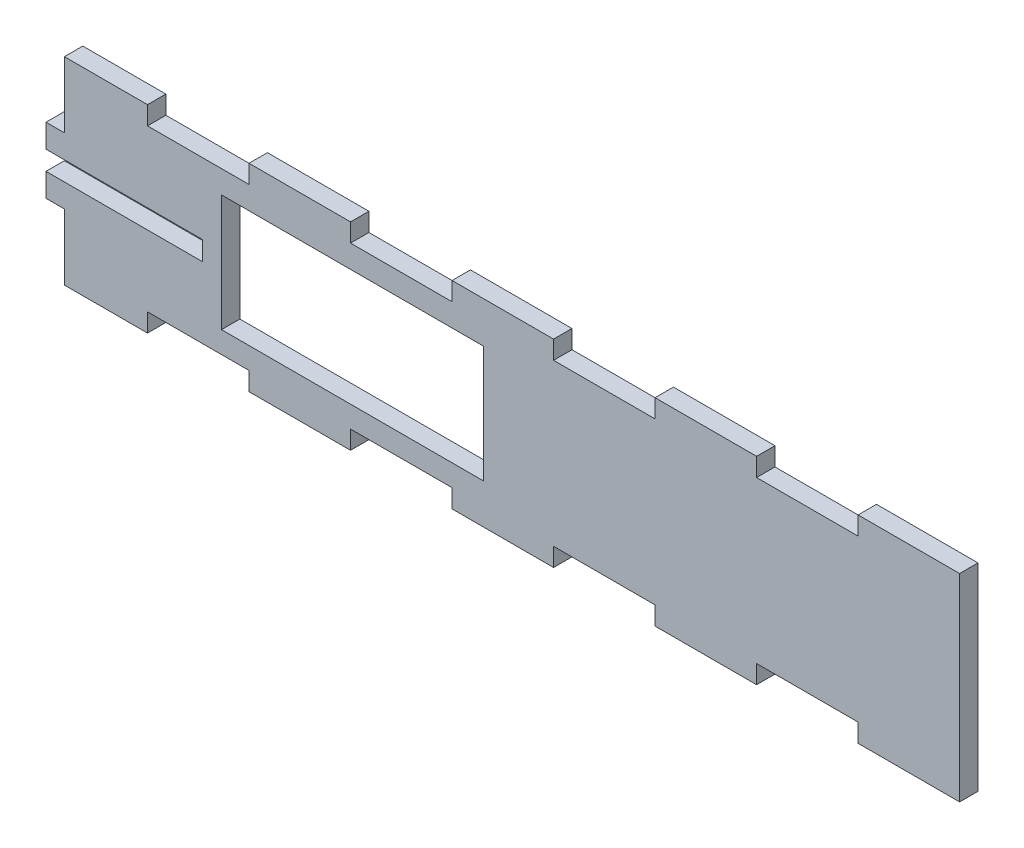
SolidWorks part; units mm, degrees
ref_plane "Front Plane" through (0, 0, 0) normal (0, 0, 1) x (1, 0, 0)
ref_plane "Top Plane" through (0, 0, 0) normal (0, 1, 0) x (1, 0, 0)
ref_plane "Right Plane" through (0, 0, 0) normal (1, 0, 0) x (0, 0, -1)
sketch "Sketch2" plane through (0, 0, 0) normal (0, 0, 1) x (1, 0, 0)
  line L1 (0, 0) -> (228.6, 0)
  line L2 (0, 0) -> (0, 49.5)
  line L3 (0, 49.5) -> (228.6, 49.5)
  line L4 (228.6, 0) -> (228.6, 49.5)
  line L5 (0, 0) -> (228.6, 49.5) construction
  line L6 (0, 49.5) -> (228.6, 0) construction
  point P4 (114.3, 24.75)
  dimension "D1" = 228.6
  dimension "D2" = 49.5
extrude "Boss-Extrude1" add sketch "Sketch2" along normal blind 4.6
sketch "Sketch4" plane through (0, 0, 4.6) normal (0, 0, 1) x (1, 0, 0)
  line L0 (0, 0) -> (228.6, 0) construction
  line L1 (25.4, 0) -> (50.8, 0)
  line L2 (25.4, 0) -> (25.4, 4.6)
  line L3 (25.4, 4.6) -> (50.8, 4.6)
  line L4 (50.8, 0) -> (50.8, 4.6)
  line L5 (25.4, 0) -> (50.8, 4.6) construction
  line L6 (25.4, 4.6) -> (50.8, 0) construction
  line L7 (0, 0) -> (25.4, 0) construction
  line L8 (76.2, 0) -> (101.6, 0)
  line L9 (76.2, 0) -> (76.2, 4.6)
  line L10 (76.2, 4.6) -> (101.6, 4.6)
  line L11 (101.6, 0) -> (101.6, 4.6)
  line L12 (76.2, 0) -> (101.6, 4.6) construction
  line L13 (76.2, 4.6) -> (101.6, 0) construction
  line L14 (127, 0) -> (152.4, 0)
  line L15 (127, 0) -> (127, 4.6)
  line L16 (127, 4.6) -> (152.4, 4.6)
  line L17 (152.4, 0) -> (152.4, 4.6)
  line L18 (127, 0) -> (152.4, 4.6) construction
  line L19 (127, 4.6) -> (152.4, 0) construction
  line L20 (177.8, 0) -> (203.2, 0)
  line L21 (177.8, 0) -> (177.8, 4.6)
  line L22 (177.8, 4.6) -> (203.2, 4.6)
  line L23 (203.2, 0) -> (203.2, 4.6)
  line L24 (177.8, 0) -> (203.2, 4.6) construction
  line L25 (177.8, 4.6) -> (203.2, 0) construction
  line L27 (50.8, 0) -> (76.2, 0) construction
  line L29 (101.6, 0) -> (127, 0) construction
  line L30 (152.4, 0) -> (177.8, 0) construction
  line L31 (203.2, 0) -> (228.6, 0) construction
  point P4 (38.1, 2.3)
  point P11 (88.9, 2.3)
  point P16 (139.7, 2.3)
  point P21 (190.5, 2.3)
  dimension "D2" = 4.6
extrude "Cut-Extrude1" cut sketch "Sketch4" against normal through all
ref_plane "Plane1" through (0, 24.75, 0) normal (0, 1, 0) x (1, 0, 0)
mirror "Mirror1" about plane through (0, 24.75, 0) normal (0, 1, 0) of "Cut-Extrude1"
sketch "Sketch5" plane through (0, 0, 0) normal (-1, 0, 0) x (0, 0, 1)
  line L0 (0, 49.5) -> (0, 0) construction
  line L1 (4.6, 49.5) -> (4.6, 0) construction
  line L2 (0, 16.5) -> (4.6, 16.5)
  line L3 (0, 16.5) -> (0, 33)
  line L4 (0, 33) -> (4.6, 33)
  line L5 (4.6, 16.5) -> (4.6, 33)
  line L6 (0, 16.5) -> (4.6, 33) construction
  line L7 (0, 33) -> (4.6, 16.5) construction
  line L8 (4.6, 49.5) -> (4.6, 33) construction
  line L9 (4.6, 16.5) -> (4.6, 0) construction
  line L11 (0, 49.5) -> (4.6, 49.5)
  line L12 (0, 49.5) -> (0, 33)
  line L13 (0, 33) -> (4.6, 33)
  line L14 (4.6, 49.5) -> (4.6, 33)
  line L15 (0, 0) -> (4.6, 0)
  line L16 (0, 0) -> (0, 16.5)
  line L17 (0, 16.5) -> (4.6, 16.5)
  line L18 (4.6, 0) -> (4.6, 16.5)
  point P6 (2.3, 24.75)
  line M7 (0, 49.5) -> (0, 0)
  line M8 (0, 0) -> (4.6, 0)
  line M9 (4.6, 0) -> (4.6, 49.5)
  line M10 (4.6, 49.5) -> (0, 49.5)
  dimension "D1" = 16.5
extrude "Cut-Extrude2" cut sketch "Sketch5" against normal blind 4.6 contours L4 M7 M9 M10 | L2 M7 M8 M9 region at (0, 8.25, 2.3) region at (0, 41.25, 2.3)
extrude "Cut-Extrude3" cut sketch "Sketch6" against normal through all
sketch "Sketch6" plane through (29.4576, -124.7153, 49.5) normal (0, 0, 1) x (1, 0, 0)
  line L2 (79.9501, 163.9153) -> (14.4501, 163.9153)
  line L3 (14.4501, 134.7153) -> (79.9501, 134.7153)
  line L4 (79.9501, 134.7153) -> (79.9501, 163.9153)
  line L5 (14.4501, 134.7153) -> (14.4501, 163.9153)
  line L6 (79.9501, 149.3153) -> (14.4501, 149.3153) construction
  point P4 (79.9501, 149.3153)
  point P5 (14.4501, 149.3153)
sketch "Sketch7" plane through (0, 0, 0) normal (0, 0, -1) x (-1, 0, 0)
  line L1 (-50.8, 4.6) -> (-25.4, 4.6) construction
  line L2 (0, 27.15) -> (0, 22.35)
  line L3 (0, 33) -> (0, 16.5) construction
  line L12 (5.58, 22.35) -> (5.58, -9.88)
  line L13 (5.58, -9.88) -> (10.38, -9.88)
  line L14 (10.38, -9.88) -> (10.38, 27.15)
  line L15 (10.38, 27.15) -> (-39.22, 27.15)
  line L16 (-39.22, 27.15) -> (-39.22, 22.35)
  line L17 (-39.22, 22.35) -> (5.58, 22.35)
  point P8 (-39.22, 24.75)
  line M50 (0, 16.5) -> (0, 33)
  dimension "D1" = 20.15
  dimension "D2" = 4.8
extrude "Cut-Extrude4" cut sketch "Sketch7" against normal through all contours L16 L17 L15 M50 region at (19.61, 24.75, 0)
equation "\"MDF\"= 4.8mm"
equation "\"Foamcore\"= 4.6mm"
equation "\"PCB\" = 1.6mm"
equation "\"GMaterial\"= \"MDF\""
equation "\"BaseWidth\" = 10in"
equation "\"SkidLength\" = 1in"
equation "\"SkidClearance\" = 0.4in"
equation "\"MotorMountLength\" = 2in"
equation "\"MotorMountWidth\" = \"GMaterial\""
equation "\"MotorMountHeight\" = 2.25in"
equation "\"UnoStackWidth\" = 77.4mm"
equation "\"UnoStackLength\" = 79.8mm"
equation "\"UnoStackHeight\" = 34.2mm"
equation "\"TallHexRiserHeight\" = 22.2mm"
equation "\"PingPongBallSize\" = 40mm"
equation "\"BarrelLength\" = 9in"
equation "\"BarrelSize\" = \"PingPongBallSize\""
equation "\"D2@Sketch2\"=\"BarrelSize\"+\"Foamcore\"*2 + \"LaserCutterOffset\""
equation "\"D1@Boss-Extrude1\"=\"Foamcore\""
equation "\"D2@Sketch4\"=\"Foamcore\""
equation "\"D1@Cut-Extrude2\"=\"Foamcore\""
equation "\"PlatformLength\" = 4in"
equation "\"PlatformWidth\" = 6in"
equation "\"WheelDiameter\"=2.99213"
equation "\"ServoMountHeight\"=2.49223"
equation "\"ServoGearHeight\" = 0.95330261in"
equation "\"ServoMountLength\"= 1.53774"
equation "\"PivotHoleRadius\"= 0.616358"
equation "\"PlatformMountHeight\" = 3.19"
equation "\"TensionOffSet\"= .3mm"
equation "\"MotorMountWedge\"=0.333333"
equation "\"LaserCutterOffset\"= .3mm"
equation "\"BumperWidth\"=11"
equation "\"PitcherWheelCompression\" = 2.5mm"
equation "\"PitchingWheelWidth\" = 26.2mm"
equation "\"PitchingWheelDiameter\" = 65.5mm"
equation "\"PitchingWheelMountOffset\" = 8.4mm"
equation "\"PitchingWheelInnerDiameter\" = 45.5mm"
equation "\"PitchingWheelBoltShoulder\" = 4.5mm"
equation "\"BrassCouplingLength\" = 18mm"
equation "\"PitchingMotorHeight\" = 57.0mm"
equation "\"PitchingMotorShaftTopHeight\" = \"PitchingMotorHeight\" - 44.1mm"
equation "\"PitchingMotorBodyHeight\" = 38mm"
equation "\"PitchingMotorTopShoulderHeight\" = 40.6mm - \"PitchingMotorBodyHeight\" "
equation "\"PitchingMotorBottomShoulderHeight\" = 40.2mm - \"PitchingMotorBodyHeight\""
equation "\"PitchingMotorBottomShaftHeight\" = \"PitchingMotorHeight\" - \"PitchingMotorShaftTopHeight\" - \"PitchingMotorTopShoulderHeight\" - \"PitchingMotorBodyHeight\" - \"PitchingMotorBottomShoulderHeight\""
equation "\"PitchingMotorShaftDiameter\" = 2.2mm"
equation "\"PitchingMotorBodyDiameter\" = 27.4mm"
equation "\"PitchingMotorTopShoulderDiameter\" = 9.8mm"
equation "\"PitchingMotorBottomShoulderDiameter\" = 9.8mm"
equation "\"BrassCouplingHexSize\" = 12mm"
equation "\"BrassCouplingBoreSize\" = 3.17mm"
equation "\"PitchingMotorMountingHoleDistance\" = 16mm"
equation "\"Acrylic\" = 4.4mm"
equation "\"PitchingMotorDistance\" = \"PitchingWheelDiameter\" + \"PingPongBallSize\" - \"PitcherWheelCompression\"*2"
equation "\"PitchingMotorPlatformOffset\"=1"
equation "\"ServoPlatformOffset\"=1.64173"
equation "\"BallBearingDiameter\" = 22mm"
equation "\"BallBearingWidth\" = 9mm"
equation "\"BallBearingHexShoulder\" = 9mm - 5.9mm"
equation "\"BallBearingHexSize\" = .36in"
equation "\"PlatformMountFootLength\"=0.857143"
equation "\"WheelWidth\"= 26mm"
equation "\"ServoMountReductionBackHeight\"=2.25"
equation "\"PlatformBottomWidthThird\" =  0.857143in"
equation "\"PlatformMountBackReductionHeight\"= 2.5in"
equation "\"PlatformMountBackReductionWidth\"= 3/7in"
equation "\"PlatformMountFrontReductionWidth\" =  1.46226in"
equation "\"PlatformMountFrontReductionHeight\" = 2.5in"
